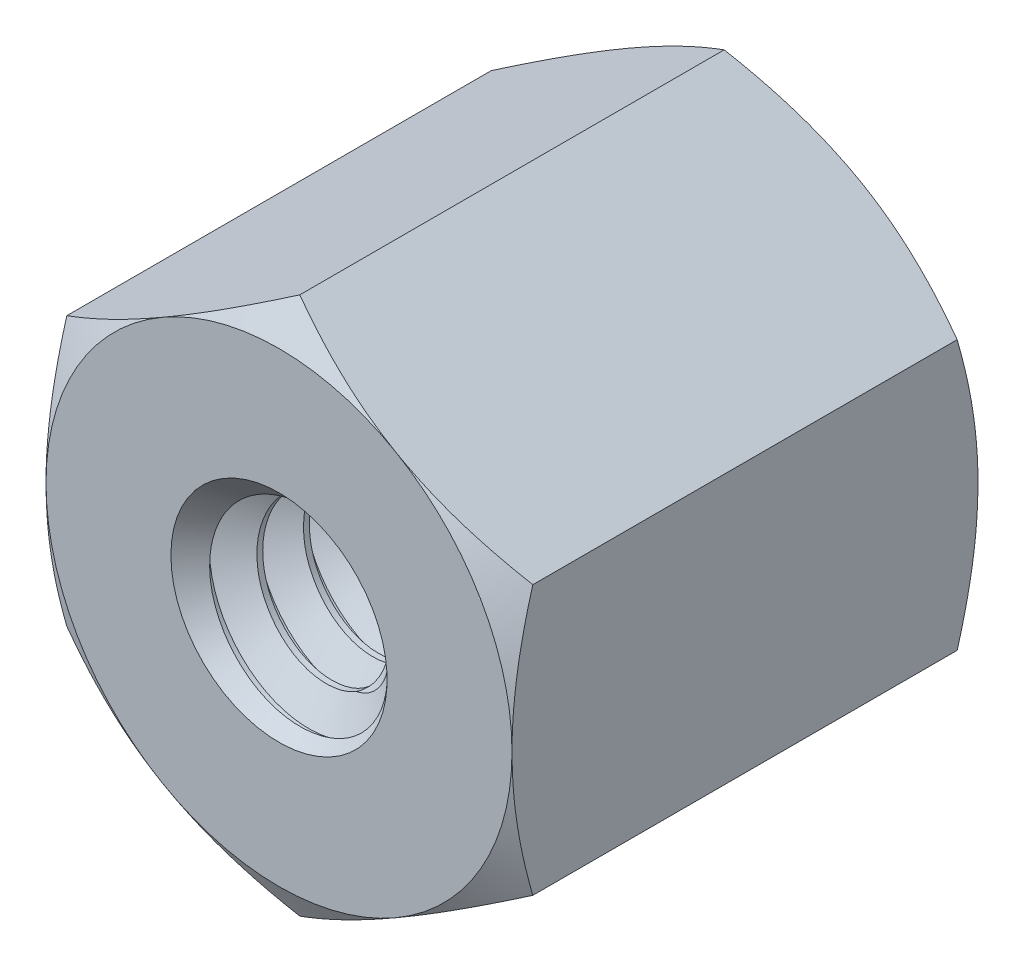
SolidWorks part; units mm, degrees
ref_plane "Front Plane" through (0, 0, 0) normal (0, 0, 1) x (1, 0, 0)
ref_plane "Top Plane" through (0, 0, 0) normal (0, 1, 0) x (1, 0, 0)
ref_plane "Right Plane" through (0, 0, 0) normal (1, 0, 0) x (0, 0, -1)
sketch "Sketch3" plane through (0, 0, 0) normal (1, 0, 0) x (0, 0, -1)
  line L0 (-3.175, 0) -> (3.175, 0) construction
  line L1 (0, 3.175) -> (0, -3.175) construction
  line L2 (-3.175, 1.4224) -> (-3.175, -1.4224) construction
  point P2 (-12.7, 0)
  point P3 (12.7, 0)
  dimension "Length" = 6.35
  dimension "Min Thread Length" = 15.875
  dimension "D1" = 15.875
  dimension "Thread Dia" = 2.8448
  dimension "Hex" = 6.35
sketch "Sketch1" plane through (0, 0, 0) normal (0, 0, 1) x (1, 0, 0)
  line L1 (0, 3.6662) -> (-3.175, 1.8331)
  line L2 (-3.175, 1.8331) -> (-3.175, -1.8331)
  line L3 (-3.175, -1.8331) -> (0, -3.6662)
  line L4 (0, -3.6662) -> (3.175, -1.8331)
  line L5 (3.175, -1.8331) -> (3.175, 1.8331)
  line L6 (3.175, 1.8331) -> (0, 3.6662)
  circle A0 centre (0, 0) radius 3.175 construction
  circle A1 centre (0, 0) radius 1.4224
extrude "Extrude1" add sketch "Sketch1" along normal up to vertex (3.175 mm away) and the other way up to vertex (3.175 mm away) up to point (0, 0, 3.175) other way up to point (0, 0, -3.175)
sketch "Sketch11" plane through (0, 0, -3.175) normal (0, 0, -1) x (-1, 0, 0)
  circle A0 centre (0, 0) radius 1.4224 construction
  circle A1 centre (0, 0) radius 1.4224
curve "Helix/Spiral1" pitch 0.635 height 6.985 radius 1.4224 centre (0, 0, -3.175) axis (0, 0, 1) start towards (0, 1, 0) parameters "Pitch"=0.635
sketch "Sketch12" plane through (0, 0, 0) normal (1, 0, 0) x (0, 0, -1)
  line L0 (3.7306, 1.4224) -> (3.175, 1.4224)
  line L1 (3.7306, 1.4224) -> (3.4925, 1.01)
  line L2 (3.4925, 1.01) -> (3.4131, 1.01)
  line L3 (3.4131, 1.01) -> (3.175, 1.4224)
  line L4 (3.4528, 1.01) -> (3.4528, 1.4224) construction
  line L5 (3.6116, 1.2162) -> (3.2941, 1.2162) construction
  dimension "D1" = 0.0794
  dimension "D2" = 0.3175
  dimension "D3" = 60
sweep "Sweep1" add profiles "Sketch12" path "Helix/Spiral1"
sketch "Sketch6" plane through (0, 0, -3.175) normal (0, 0, -1) x (-1, 0, 0)
  line L6 (0, 3.6662) -> (-3.175, 1.8331)
  line L7 (-3.175, 1.8331) -> (-3.175, -1.8331)
  line L8 (-3.175, -1.8331) -> (0, -3.6662)
  line L9 (0, -3.6662) -> (3.175, -1.8331)
  line L10 (3.175, -1.8331) -> (3.175, 1.8331)
  line L11 (3.175, 1.8331) -> (0, 3.6662)
  line L12 (0, 3.6662) -> (-3.175, 1.8331)
  line L13 (-3.175, 1.8331) -> (-3.175, -1.8331)
  line L14 (-3.175, -1.8331) -> (0, -3.6662)
  line L15 (0, -3.6662) -> (3.175, -1.8331)
  line L16 (3.175, -1.8331) -> (3.175, 1.8331)
  line L17 (3.175, 1.8331) -> (0, 3.6662)
  dimension "D1" = 0
extrude "Extrude2" cut sketch "Sketch6" along normal through all
sketch "Sketch7" plane through (0, 0, -3.175) normal (0, 0, -1) x (-1, 0, 0)
  circle A2 centre (0, 0) radius 1.4732
  circle A3 centre (0, 0) radius 1.4732
  dimension "D1" = 0.0508
extrude "Extrude3" cut sketch "Sketch7" against normal through all draft 43
sketch "Sketch8" plane through (0, 0, -3.175) normal (0, 0, -1) x (-1, 0, 0)
  circle A0 centre (0, 0) radius 3.175 construction
  circle A1 centre (0, 0) radius 3.175
extrude "Extrude4" cut sketch "Sketch8" against normal through all draft 60 flip side to cut
mirror "Mirror1" about plane through (0, 0, 0) normal (0, 0, 1) of "Extrude2", "Extrude3", "Extrude4"
sketch "Sketch9" [suppressed] plane through (0, 0, 0) normal (1, 0, 0) x (0, 0, -1)
  line L1 (-22.225, 3.2258) -> (22.225, 3.2258)
  line L2 (-22.225, 3.2258) -> (-22.225, 0)
  line L3 (-22.225, 0) -> (22.225, 0)
  line L4 (22.225, 3.2258) -> (22.225, 0)
  line L7 (-38.1, 0) -> (38.1, 0) construction
revolve "Revolve" [suppressed] add sketch "Sketch9" angle 360 about L0
sketch "Sketch10" [suppressed] plane through (0, 0, 0) normal (1, 0, 0) x (0, 0, -1)
  line L0 (38.1, 3.175) -> (22.225, 3.175)
  line L1 (-38.1, 3.175) -> (-22.225, 3.175)
  line L2 (22.225, 3.175) -> (22.225, -3.175)
  line L3 (-38.1, -3.2258) -> (-22.225, -3.2258)
  line L4 (-22.225, 3.175) -> (-22.225, -3.2258)
  line L5 (22.225, -3.175) -> (38.1, -3.175)
equation "\"D1@Sketch3\" = \"Min Thread Length@Sketch3\""
equation "\"D3@Helix/Spiral1\" = \"Length@Sketch3\"+\"Pitch@Helix/Spiral1\""
equation "\"D1@Sketch12\" = \"Pitch@Helix/Spiral1\"*.125"
equation "\"D2@Sketch12\" = \"Pitch@Helix/Spiral1\"*.5"
